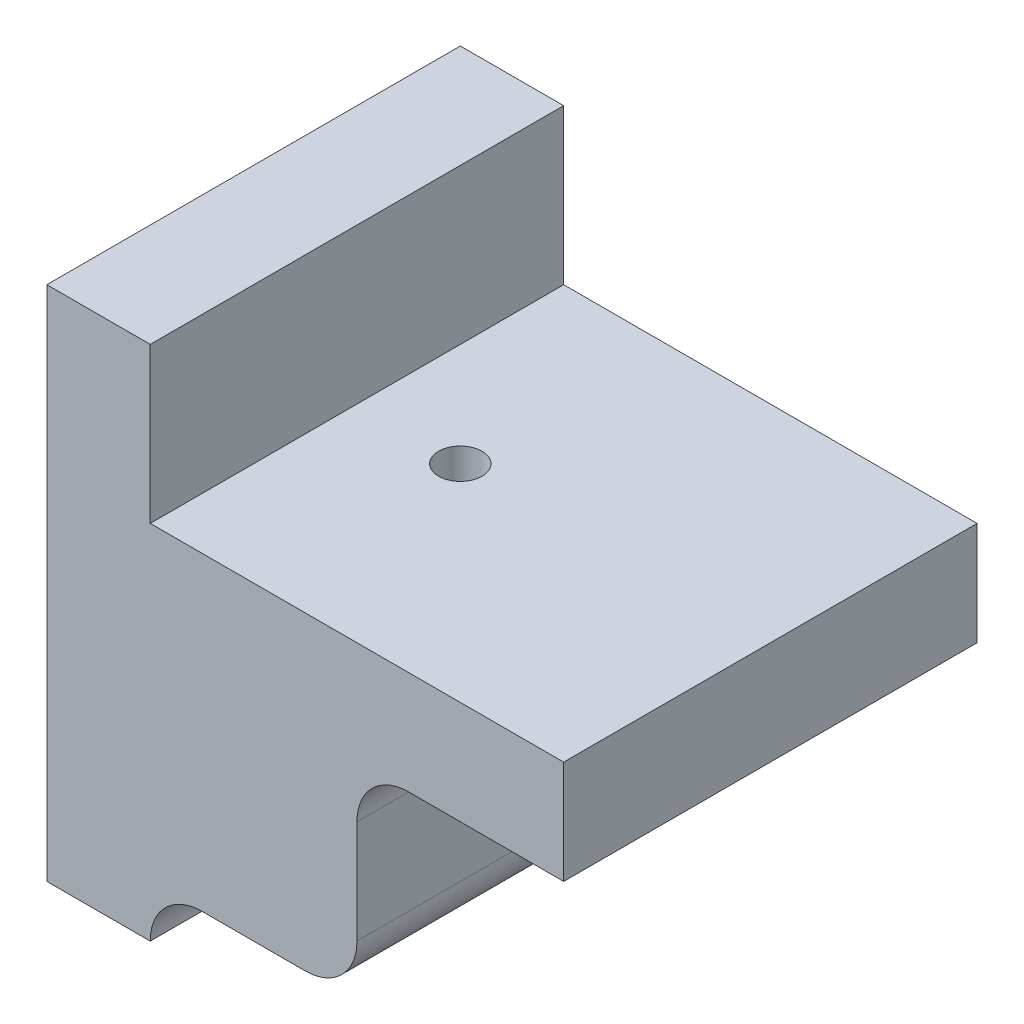
SolidWorks part; units mm, degrees
ref_plane "Plan de face" through (0, 0, 0) normal (0, 0, 1) x (1, 0, 0)
ref_plane "Plan de dessus" through (0, 0, 0) normal (0, 1, 0) x (1, 0, 0)
ref_plane "Plan de droite" through (0, 0, 0) normal (1, 0, 0) x (0, 0, -1)
sketch "Esquisse1" plane through (0, 0, 0) normal (0, 0, 1) x (1, 0, 0)
  line L0 (-20, 15) -> (-20, -35)
  line L1 (-20, -35) -> (-10, -35)
  line L2 (-10, -35) -> (-10, -30)
  line L3 (-10, -30) -> (10, -30)
  line L4 (10, -30) -> (10, -10)
  line L5 (10, -10) -> (30, -10)
  line L6 (30, -10) -> (30, 0)
  line L7 (30, 0) -> (-10, 0)
  line L8 (-10, 0) -> (-10, 15)
  line L9 (-10, 15) -> (-20, 15)
  dimension "D1" = 10
  dimension "D2" = 50
  dimension "D3" = 10
  dimension "D4" = 5
  dimension "D5" = 20
  dimension "D6" = 20
  dimension "D7" = 20
  dimension "D8" = 10
  dimension "D9" = 10
extrude "Boss.-Extru.1" add sketch "Esquisse1" along normal mid plane 40
fillet "Congé1" radius 5 3 edges at (-10, -30, 0) (10, -10, 0) (10, -30, 0)
hole_wizard "Trou taraudé M51" positions "Esquisse2" profile "Esquisse3" tap size "M5" standard "ISO"
sketch "Esquisse2" plane through (0, 0, 0) normal (0, 1, 0) x (1, 0, 0)
  point P0 (0, 0)
cosmetic thread "Filetage de perçage1" parameters "D1"=10, "D2"=5
sketch "Esquisse3" plane through (0, 0, 0) normal (1, 0, 0) x (0, 0, 1)
  line L0 (0, 0) -> (0, 26.2618)
  line L1 (0, 26.2618) -> (2.1, 25)
  line L2 (2.1, 25) -> (2.1, 0)
  line L5 (2.1, 0) -> (0, 0)
  line L10 (0, 26.2618) -> (-2.1, 25) construction
  line L11 (0, -6.35) -> (0, 107.95) construction
  dimension "Diamètre du trou pour taraudage" = 4.2
  dimension "Profondeur du trou pour taraudage" = 25
  dimension "Angle de pointe" = 118
